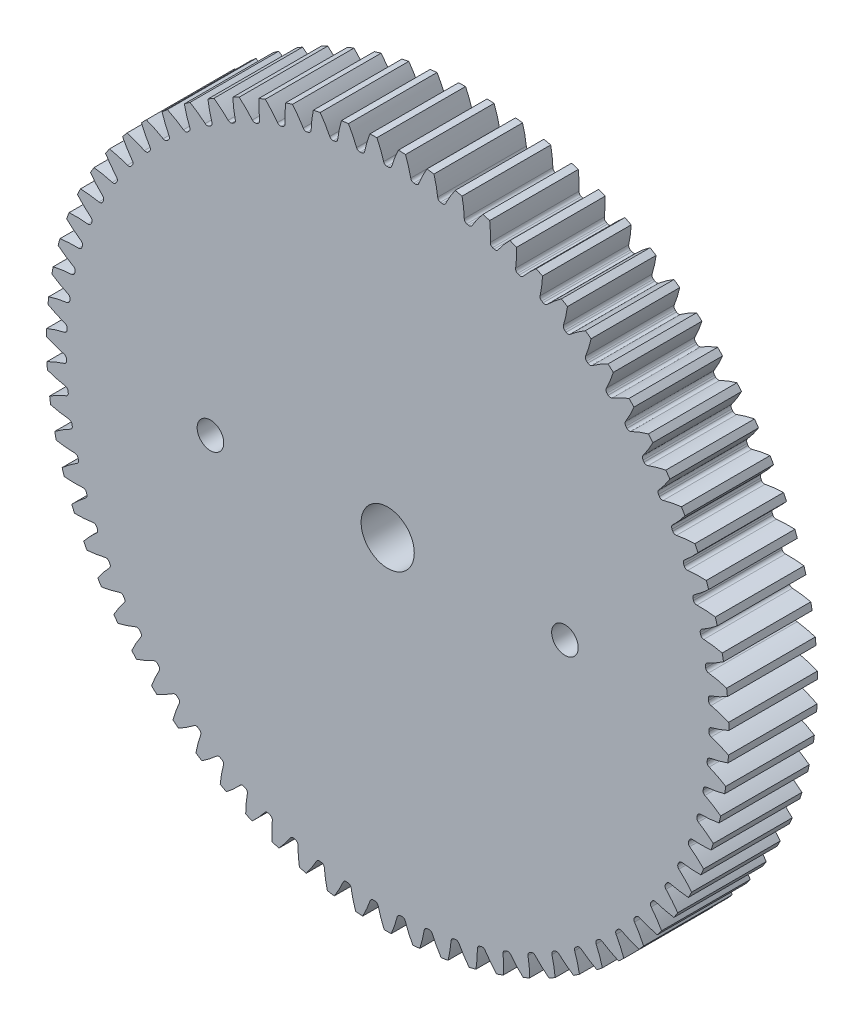
SolidWorks part; units mm, degrees
ref_plane "Front" through (0, 0, 0) normal (0, 0, 1) x (1, 0, 0)
ref_plane "Top" through (0, 0, 0) normal (0, 1, 0) x (1, 0, 0)
ref_plane "Right" through (0, 0, 0) normal (1, 0, 0) x (0, 0, -1)
ref_axis "Axis1" through (0, 0, -80.9) along (0, 0, 1)
sketch "草图1" plane through (0, 0, 0) normal (0, 0, 1) x (1, 0, 0)
  circle A0 centre (0, 0) radius 38.5
extrude "LaShenA" add sketch "草图1" along normal blind 10
sketch "SketchA" plane through (0, 0, 10) normal (0, 0, 1) x (1, 0, 0)
  line L0 (0, 0) -> (0, 38.5) construction
  arc A0 (0.0916, 36.2499) -> (-0.0916, 36.2499) centre (0, 0) ccw
  arc A1 (1.4788, 39.0083) -> (-1.4788, 39.0083) centre (0, 0) ccw
  arc A2 (-0.0916, 36.2499) -> (-0.4576, 36.5243) centre (-0.0925, 36.6299) cw
  arc A3 (0.4576, 36.5243) -> (0.0916, 36.2499) centre (0.0925, 36.6299) cw
  circle A4 centre (0, 0) radius 35.2385 construction
  circle A5 centre (0, 0) radius 38.5 construction
  circle A6 centre (0, 0) radius 36.25 construction
  circle A7 centre (0, 0) radius 37.5 construction
  spline S0 degree 3 poles (0.4576, 36.5243) (0.4608, 36.5355) (0.4704, 36.5685) (0.4866, 36.6238) (0.5068, 36.6905) (0.5279, 36.7588) (0.5499, 36.8285) (0.573, 36.8996) (0.5971, 36.9722) (0.6222, 37.0462) (0.6484, 37.1216) (0.6757, 37.1984) (0.7041, 37.2766) (0.7336, 37.3561) (0.7642, 37.437) (0.796, 37.5193) (0.829, 37.6029) (0.8632, 37.6879) (0.8986, 37.7741) (0.9352, 37.8617) (0.9731, 37.9505) (1.0123, 38.0406) (1.0528, 38.132) (1.0947, 38.2246) (1.1378, 38.3185) (1.1823, 38.4136) (1.2282, 38.5099) (1.2755, 38.6073) (1.3242, 38.706) (1.3915, 38.8401) (1.4435, 38.9409) (1.4788, 39.0083) knots 0.096666 0.096666 0.096666 0.096666 0.108398 0.131256 0.154677 0.178662 0.20321 0.228321 0.253996 0.280234 0.307036 0.334401 0.362329 0.39082 0.419875 0.449493 0.479675 0.51042 0.541728 0.5736 0.606035 0.639033 0.672595 0.70672 0.741408 0.77666 0.812475 0.848853 0.885795 0.9233 1 1 1 1
  spline S1 degree 3 poles (-0.4576, 36.5243) (-0.4608, 36.5355) (-0.4704, 36.5685) (-0.4866, 36.6238) (-0.5068, 36.6905) (-0.5279, 36.7588) (-0.5499, 36.8285) (-0.573, 36.8996) (-0.5971, 36.9722) (-0.6222, 37.0462) (-0.6484, 37.1216) (-0.6757, 37.1984) (-0.7041, 37.2766) (-0.7336, 37.3561) (-0.7642, 37.437) (-0.796, 37.5193) (-0.829, 37.6029) (-0.8632, 37.6879) (-0.8986, 37.7741) (-0.9352, 37.8617) (-0.9731, 37.9505) (-1.0123, 38.0406) (-1.0528, 38.132) (-1.0947, 38.2246) (-1.1378, 38.3185) (-1.1823, 38.4136) (-1.2282, 38.5099) (-1.2755, 38.6073) (-1.3242, 38.706) (-1.3915, 38.8401) (-1.4435, 38.9409) (-1.4788, 39.0083) knots 0.096666 0.096666 0.096666 0.096666 0.108398 0.131256 0.154677 0.178662 0.20321 0.228321 0.253996 0.280234 0.307036 0.334401 0.362329 0.39082 0.419875 0.449493 0.479675 0.51042 0.541728 0.5736 0.606035 0.639033 0.672595 0.70672 0.741408 0.77666 0.812475 0.848853 0.885795 0.9233 1 1 1 1
  dimension "D1" = 0.38
  dimension "Db" = 70.4769
  dimension "Da" = 77
  dimension "Df" = 72.5
  dimension "Dn" = 75
extrude "Cut-ExtrudeA" cut sketch "SketchA" against normal blind 30
pattern_circular "阵列(圆周)1" count 75 over 360 about axis through (0, 0, -80.9) along (0, 0, 1) of "Cut-ExtrudeA"
sketch "草图3" plane through (0, 0, 10) normal (0, 0, 1) x (1, 0, 0)
  line L0 (0, 0) -> (-20, 0) construction
  line L1 (0, 0) -> (20, 0) construction
  circle A0 centre (0, 0) radius 3
  circle A1 centre (-20, 0) radius 1.5
  circle A2 centre (20, 0) radius 1.5
  dimension "D1" = 20
  dimension "D2" = 20
extrude "切除-拉伸2" cut sketch "草图3" against normal blind 10
